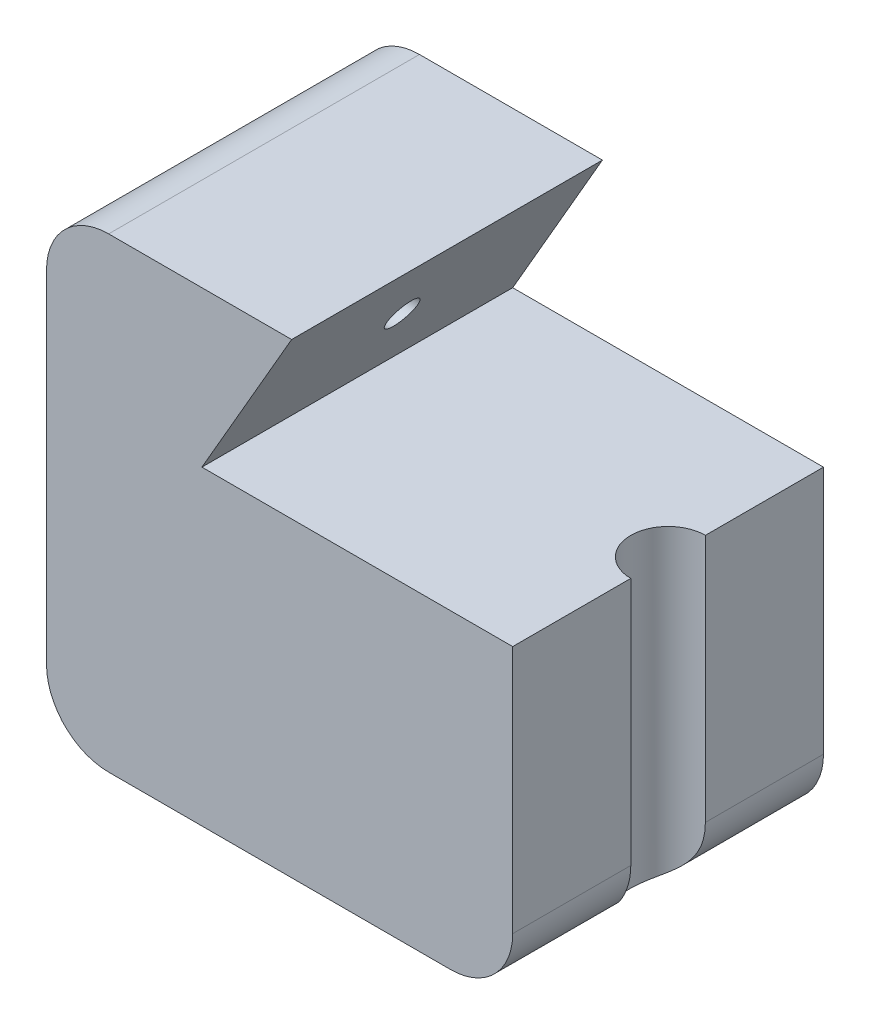
SolidWorks part; units mm, degrees
ref_plane "Front Plane" through (0, 0, 0) normal (0, 0, 1) x (1, 0, 0)
ref_plane "Top Plane" through (0, 0, 0) normal (0, 1, 0) x (1, 0, 0)
ref_plane "Right Plane" through (0, 0, 0) normal (1, 0, 0) x (0, 0, -1)
sketch "Sketch1" plane through (0, 0, 0) normal (0, 0, 1) x (1, 0, 0)
  line L0 (0, 10) -> (0, 65)
  line L1 (10, 75) -> (39.4338, 75)
  line L2 (39.4338, 75) -> (25, 50)
  line L3 (25, 50) -> (75, 50)
  line L4 (75, 50) -> (75, 10)
  line L5 (65, 0) -> (10, 0)
  line L6 (75, -958.2633) -> (75, 49041.7367) construction
  arc A0 (0, 10) -> (10, 0) centre (10, 10) ccw
  arc A1 (65, 0) -> (75, 10) centre (65, 10) ccw
  arc A2 (0, 65) -> (10, 75) centre (10, 65) cw
  point P11 (0, 0)
  dimension "D6" = 10
  dimension "D1" = 60
  dimension "D3" = 75
  dimension "D2" = 25
  dimension "D4" = 75
  dimension "D5" = 50
extrude "Boss-Extrude1" add sketch "Sketch1" along normal blind 50
sketch "Sketch2" plane through (0, 50, 0) normal (0, 1, 0) x (1, 0, 0)
  line L1 (75, -50) -> (75, 0) construction
  circle A0 centre (75, -25) radius 6
  point P8 (75, -25)
  dimension "D1" = 12
extrude "Cut-Extrude1" cut sketch "Sketch2" against normal up to surface (50 mm away) up to face at (37.5, 0, 25)
sketch "Sketch3" plane through (0, 0, 0) normal (-1, 0, 0) x (0, 0, 1)
  line L0 (25, -900) -> (25, 49100) construction
  line L1 (50, 75) -> (0, 75) construction
  circle A0 centre (25, 62.5) radius 2.5
  point P5 (25, 75)
  dimension "D1" = 5
  dimension "D2" = 12.5
extrude "Cut-Extrude2" cut sketch "Sketch3" against normal up to surface (75 mm away) up to face at (75, 30, 9.5)
equation "\"ShaftDiameter\"= 12mm"
equation "\"PendulumDiameter\"=12mm"
equation "\"PendulumLength\"= 140mm"
equation "\"EncoderOuterDiameter\"=1.5"
equation "\"EncoderShaftDiameter\"= 6mm"
equation "\"EncoderShaftLength\"=15mm+.5in+3mm"
equation "\"D1@Sketch2\"=\"PendulumDiameter\""
equation "\"PendulumHolderangle\"=60"
equation "\"D1@Sketch1\"=\"PendulumHolderangle\""
equation "\"PendulumholderBottomHeight\"= 75"
equation "\"D3@Sketch1\"=\"PendulumholderBottomHeight\""
equation "\"PendulumholderBottomWidth\"= 75"
equation "\"D4@Sketch1\"=\"PendulumholderBottomWidth\""
equation "\"PendulumholderHeight\"=25"
equation "\"D2@Sketch1\"=\"PendulumholderHeight\""
equation "\"BearingOutsideDiameter\"=21mm"
equation "\"PendulumHolderWidth\"= 100mm"
equation "\"D5@Sketch1\"= \"PendulumHolderWidth\" / 2"
equation "\"ScrewHole\"= 5mm"
equation "\"ShaftHeightFromTSlot\"= 100mm"
equation "\"BearingThickness\"= 5mm"
equation "\"SlipRingOuterDiameter\"=56mm"
equation "\"SlipringBigThickness\"=25mm"
equation "\"SlipringSmallThickness\"=8.5mm"
equation "\"Tol\"=2mm"
equation "\"D1@Sketch3\"=\"ScrewHole\""
